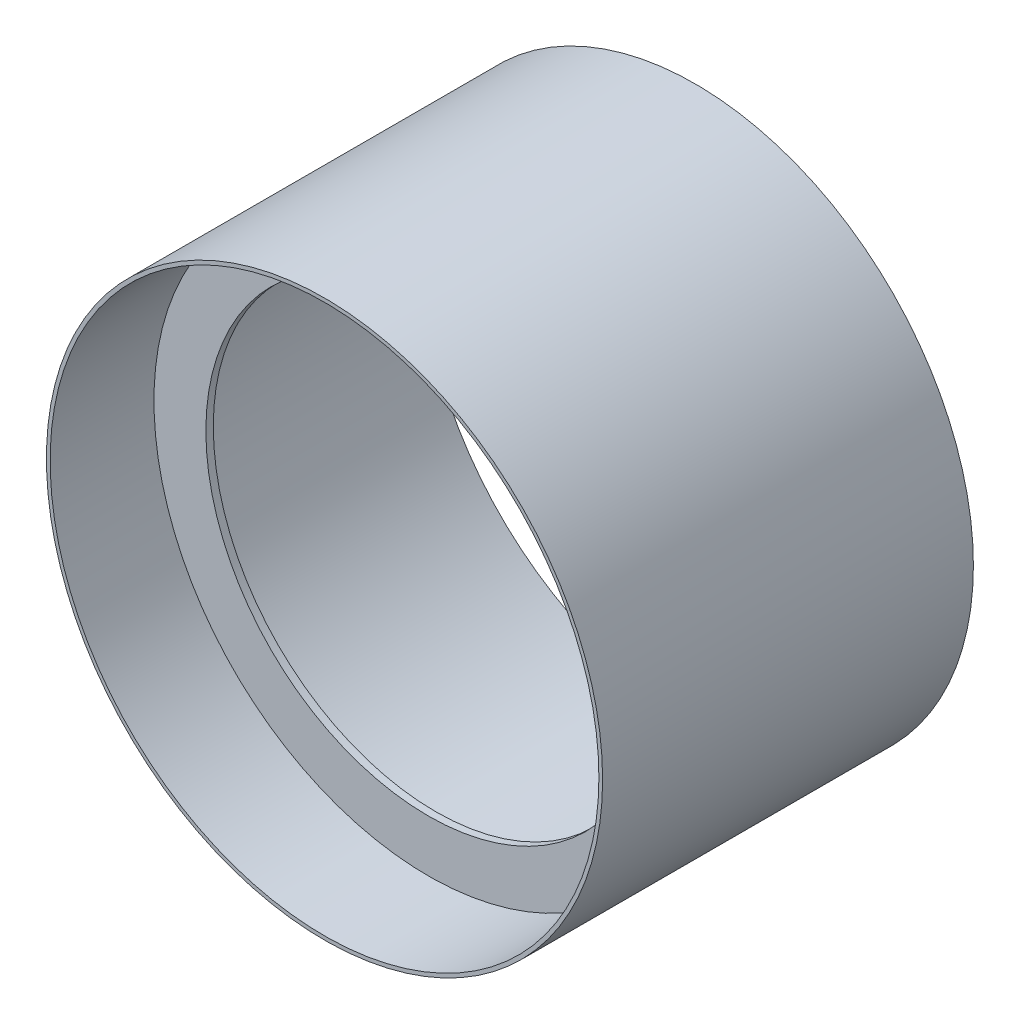
SolidWorks part; units mm, degrees
ref_plane "前视基准面" through (0, 0, 0) normal (0, 0, 1) x (1, 0, 0)
ref_plane "上视基准面" through (0, 0, 0) normal (0, 1, 0) x (1, 0, 0)
ref_plane "右视基准面" through (0, 0, 0) normal (1, 0, 0) x (0, 0, -1)
sketch "草图1" plane through (0, 0, 0) normal (0, 0, 1) x (1, 0, 0)
  circle A0 centre (0, 0) radius 75
  dimension "D1" = 150
extrude "凸台-拉伸1" add sketch "草图1" along normal blind 100
shell "抽壳1" thickness 1 removed face at (75, 0, 0) removed face at (75, 0, 100)
ref_plane "基准面1" through (0, 0, 70) normal (0, 0, 1) x (1, 0, 0)
sketch "草图2" plane through (0, 0, 70) normal (0, 0, 1) x (1, 0, 0)
  circle A0 centre (0, 0) radius 75
  circle A1 centre (0, 0) radius 60
  dimension "D1" = 150
  dimension "D2" = 120
extrude "凸台-拉伸2" add sketch "草图2" along normal blind 2
